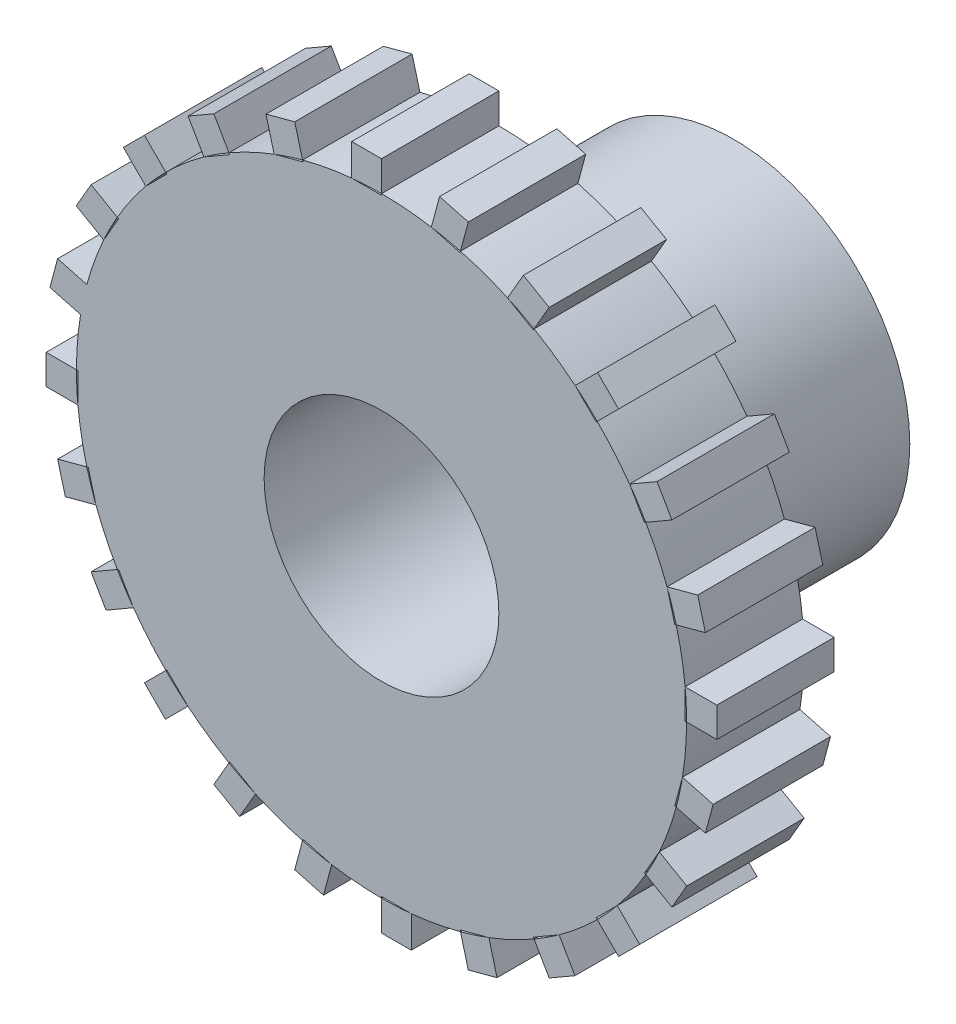
SolidWorks part; units mm, degrees
ref_plane "Front Plane" through (0, 0, 0) normal (0, 0, 1) x (1, 0, 0)
ref_plane "Top Plane" through (0, 0, 0) normal (0, 1, 0) x (1, 0, 0)
ref_plane "Right Plane" through (0, 0, 0) normal (1, 0, 0) x (0, 0, -1)
sketch "Sketch1" plane through (0, 0, 0) normal (0, 0, 1) x (1, 0, 0)
  circle A0 centre (0, 0) radius 6.35
  circle A1 centre (0, 0) radius 9.525
  dimension "D1" = 12.7
  dimension "D2" = 19.05
extrude "Boss-Extrude1" add sketch "Sketch1" along normal blind 12.7
sketch "Sketch2" plane through (0, 0, 12.7) normal (0, 0, 1) x (1, 0, 0)
  line L0 (2.6952, 16.2787) -> (3.1391, 17.9355)
  line L1 (-1.6099, 16.4215) -> (0, 16.4215)
  line L2 (-1.6099, 16.4215) -> (-1.6099, 18.1368)
  line L3 (-1.6099, 18.1368) -> (0, 18.1368)
  line L4 (0, 16.4215) -> (0, 18.1368)
  line L5 (2.6952, 16.2787) -> (4.2502, 15.862)
  line L6 (4.2502, 15.862) -> (4.6942, 17.5188)
  line L7 (3.1391, 17.9355) -> (4.6942, 17.5188)
  line L8 (6.8166, 15.0264) -> (7.6742, 16.5119)
  line L9 (6.8166, 15.0264) -> (8.2108, 14.2215)
  line L10 (8.2108, 14.2215) -> (9.0684, 15.707)
  line L11 (7.6742, 16.5119) -> (9.0684, 15.707)
  line L12 (10.4734, 12.7502) -> (11.6863, 13.963)
  line L13 (10.4734, 12.7502) -> (11.6118, 11.6118)
  line L14 (11.6118, 11.6118) -> (12.8247, 12.8247)
  line L15 (11.6863, 13.963) -> (12.8247, 12.8247)
  line L16 (13.4165, 9.605) -> (14.902, 10.4626)
  line L17 (13.4165, 9.605) -> (14.2215, 8.2108)
  line L18 (14.2215, 8.2108) -> (15.707, 9.0684)
  line L19 (14.902, 10.4626) -> (15.707, 9.0684)
  line L20 (15.4453, 5.8052) -> (17.1022, 6.2492)
  line L21 (15.4453, 5.8052) -> (15.862, 4.2502)
  line L22 (15.862, 4.2502) -> (17.5188, 4.6942)
  line L23 (17.1022, 6.2492) -> (17.5188, 4.6942)
  line L24 (16.4215, 1.6099) -> (18.1368, 1.6099)
  line L25 (16.4215, 1.6099) -> (16.4215, 0)
  line L26 (16.4215, 0) -> (18.1368, 0)
  line L27 (18.1368, 1.6099) -> (18.1368, 0)
  line L28 (16.2787, -2.6952) -> (17.9355, -3.1391)
  line L29 (16.2787, -2.6952) -> (15.862, -4.2502)
  line L30 (15.862, -4.2502) -> (17.5188, -4.6942)
  line L31 (17.9355, -3.1391) -> (17.5188, -4.6942)
  line L32 (15.0264, -6.8166) -> (16.5119, -7.6742)
  line L33 (15.0264, -6.8166) -> (14.2215, -8.2108)
  line L34 (14.2215, -8.2108) -> (15.707, -9.0684)
  line L35 (16.5119, -7.6742) -> (15.707, -9.0684)
  line L36 (12.7502, -10.4734) -> (13.963, -11.6863)
  line L37 (12.7502, -10.4734) -> (11.6118, -11.6118)
  line L38 (11.6118, -11.6118) -> (12.8247, -12.8247)
  line L39 (13.963, -11.6863) -> (12.8247, -12.8247)
  line L40 (9.605, -13.4165) -> (10.4626, -14.902)
  line L41 (9.605, -13.4165) -> (8.2108, -14.2215)
  line L42 (8.2108, -14.2215) -> (9.0684, -15.707)
  line L43 (10.4626, -14.902) -> (9.0684, -15.707)
  line L44 (5.8052, -15.4453) -> (6.2492, -17.1022)
  line L45 (5.8052, -15.4453) -> (4.2502, -15.862)
  line L46 (4.2502, -15.862) -> (4.6942, -17.5188)
  line L47 (6.2492, -17.1022) -> (4.6942, -17.5188)
  line L48 (1.6099, -16.4215) -> (1.6099, -18.1368)
  line L49 (1.6099, -16.4215) -> (0, -16.4215)
  line L50 (0, -16.4215) -> (0, -18.1368)
  line L51 (1.6099, -18.1368) -> (0, -18.1368)
  line L52 (-2.6952, -16.2787) -> (-3.1391, -17.9355)
  line L53 (-2.6952, -16.2787) -> (-4.2502, -15.862)
  line L54 (-4.2502, -15.862) -> (-4.6942, -17.5188)
  line L55 (-3.1391, -17.9355) -> (-4.6942, -17.5188)
  line L56 (-6.8166, -15.0264) -> (-7.6742, -16.5119)
  line L57 (-6.8166, -15.0264) -> (-8.2108, -14.2215)
  line L58 (-8.2108, -14.2215) -> (-9.0684, -15.707)
  line L59 (-7.6742, -16.5119) -> (-9.0684, -15.707)
  line L60 (-10.4734, -12.7502) -> (-11.6863, -13.963)
  line L61 (-10.4734, -12.7502) -> (-11.6118, -11.6118)
  line L62 (-11.6118, -11.6118) -> (-12.8247, -12.8247)
  line L63 (-11.6863, -13.963) -> (-12.8247, -12.8247)
  line L64 (-13.4165, -9.605) -> (-14.902, -10.4626)
  line L65 (-13.4165, -9.605) -> (-14.2215, -8.2108)
  line L66 (-14.2215, -8.2108) -> (-15.707, -9.0684)
  line L67 (-14.902, -10.4626) -> (-15.707, -9.0684)
  line L68 (-15.4453, -5.8052) -> (-17.1022, -6.2492)
  line L69 (-15.4453, -5.8052) -> (-15.862, -4.2502)
  line L70 (-15.862, -4.2502) -> (-17.5188, -4.6942)
  line L71 (-17.1022, -6.2492) -> (-17.5188, -4.6942)
  line L72 (-16.4215, -1.6099) -> (-18.1368, -1.6099)
  line L73 (-16.4215, -1.6099) -> (-16.4215, 0)
  line L74 (-16.4215, 0) -> (-18.1368, 0)
  line L75 (-18.1368, -1.6099) -> (-18.1368, 0)
  line L76 (-16.2787, 2.6952) -> (-17.9355, 3.1391)
  line L77 (-16.2787, 2.6952) -> (-15.862, 4.2502)
  line L78 (-15.862, 4.2502) -> (-17.5188, 4.6942)
  line L79 (-17.9355, 3.1391) -> (-17.5188, 4.6942)
  line L80 (-15.0264, 6.8166) -> (-16.5119, 7.6742)
  line L81 (-15.0264, 6.8166) -> (-14.2215, 8.2108)
  line L82 (-14.2215, 8.2108) -> (-15.707, 9.0684)
  line L83 (-16.5119, 7.6742) -> (-15.707, 9.0684)
  line L84 (-12.7502, 10.4734) -> (-13.963, 11.6863)
  line L85 (-12.7502, 10.4734) -> (-11.6118, 11.6118)
  line L86 (-11.6118, 11.6118) -> (-12.8247, 12.8247)
  line L87 (-13.963, 11.6863) -> (-12.8247, 12.8247)
  line L88 (-9.605, 13.4165) -> (-10.4626, 14.902)
  line L89 (-9.605, 13.4165) -> (-8.2108, 14.2215)
  line L90 (-8.2108, 14.2215) -> (-9.0684, 15.707)
  line L91 (-10.4626, 14.902) -> (-9.0684, 15.707)
  line L92 (-5.8052, 15.4453) -> (-6.2492, 17.1022)
  line L93 (-5.8052, 15.4453) -> (-4.2502, 15.862)
  line L94 (-4.2502, 15.862) -> (-4.6942, 17.5188)
  line L95 (-6.2492, 17.1022) -> (-4.6942, 17.5188)
  circle A0 centre (0, 0) radius 16.5003
  point P101 (0, 0)
  circle M97 centre (0, 0) radius 9.525
  circle M98 centre (0, 0) radius 6.35
  dimension "D1" = 24
extrude "Boss-Extrude2" add sketch "Sketch2" along normal blind 6.35 contours L25 A0 L22 L21 L18 L17 L14 L13 L10 L9 L6 L5 L4 L1 L94 L93 L90 L89 L86 L85 L82 L81 L78 L77 L74 L73 L70 L69 L66 L65 L62 L61 L58 L57 L54 | M97 M98 | A0 L82 L83 L80 | A0 L86 L87 L84 | A0 L90 L91 L88 | A0 L94 L95 L92 | A0 L4 L3 L2 | A0 L6 L7 L0 | A0 L10 L11 L8 | A0 L14 L15 L12 | A0 L18 L19 L16 | A0 L22 L23 L20 | A0 L26 L27 L24 | A0 L30 L31 L28 | A0 L34 L35 L32 | A0 L38 L39 L36 | A0 L42 L43 L40 | A0 L46 L47 L44 | A0 L50 L51 L48 | A0 L54 L55 L52 | A0 L58 L59 L56 | A0 L62 L63 L60 | A0 L66 L67 L64 | A0 L70 L71 L68 | A0 L74 L75 L72 | L79 L78 L77 L76 region at (3.6953, 16.9256, 12.7) region at (3.3519, 15.6195, 12.7) region at (-0.8113, 17.3053, 12.7) region at (7.95, 15.3925, 12.7) region at (-5.2626, 16.5056, 12.7) region at (11.663, 12.8103, 12.7) region at (-9.3552, 14.5812, 12.7) region at (14.5812, 9.3552, 12.7) region at (-12.8103, 11.663, 12.7) region at (16.5056, 5.2626, 12.7) region at (-15.3925, 7.95, 12.7) region at (17.3053, 0.8113, 12.7) region at (16.9256, -3.6953, 12.7) region at (-17.3053, -0.8113, 12.7) region at (15.3925, -7.95, 12.7) region at (-16.5056, -5.2626, 12.7) region at (12.8103, -11.663, 12.7) region at (-14.5812, -9.3552, 12.7) region at (9.3552, -14.5812, 12.7) region at (-11.663, -12.8103, 12.7) region at (5.2626, -16.5056, 12.7) region at (-7.95, -15.3925, 12.7) region at (0.8113, -17.3053, 12.7) region at (-3.6953, -16.9256, 12.7) region at (-9.2556, 0, 12.7)
